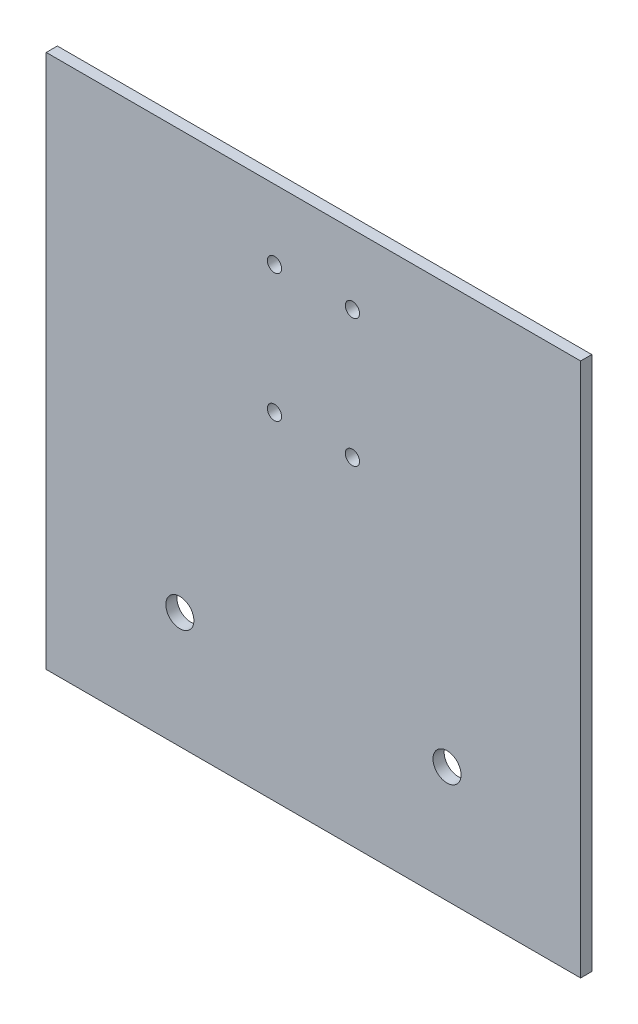
SolidWorks part; units mm, degrees
ref_plane "Front Plane" through (0, 0, 0) normal (0, 0, 1) x (1, 0, 0)
ref_plane "Top Plane" through (0, 0, 0) normal (0, 1, 0) x (1, 0, 0)
ref_plane "Right Plane" through (0, 0, 0) normal (1, 0, 0) x (0, 0, -1)
sketch "Sketch1" plane through (0, 0, 0) normal (0, 0, 1) x (1, 0, 0)
  line L1 (76.2, -76.2) -> (-76.2, -76.2)
  line L2 (76.2, -76.2) -> (76.2, 76.2)
  line L3 (76.2, 76.2) -> (-76.2, 76.2)
  line L4 (-76.2, -76.2) -> (-76.2, 76.2)
  line L5 (76.2, -76.2) -> (-76.2, 76.2) construction
  line L6 (76.2, 76.2) -> (-76.2, -76.2) construction
  point P0 (0, 0)
extrude "Boss-Extrude1" add sketch "Sketch1" along normal blind 3.175
sketch "Sketch2" plane through (0, 0, 3.175) normal (0, 0, 1) x (1, 0, 0)
  line L0 (-76.2, 76.2) -> (-76.2, -76.2) construction
  line L1 (-16.6613, 15.8694) -> (16.6613, 15.8694)
  line L2 (-16.6613, 15.8694) -> (-16.6613, 60.3306)
  line L3 (-16.6613, 60.3306) -> (16.6613, 60.3306)
  line L4 (16.6613, 15.8694) -> (16.6613, 60.3306)
  line L5 (-16.6613, 15.8694) -> (16.6613, 60.3306) construction
  line L6 (-16.6613, 60.3306) -> (16.6613, 15.8694) construction
  line L7 (-11.1125, 19.8374) -> (11.1125, 19.8374)
  line L8 (-11.1125, 19.8374) -> (-11.1125, 56.3626)
  line L9 (-11.1125, 56.3626) -> (11.1125, 56.3626)
  line L10 (11.1125, 19.8374) -> (11.1125, 56.3626)
  line L11 (-11.1125, 19.8374) -> (11.1125, 56.3626) construction
  line L12 (-11.1125, 56.3626) -> (11.1125, 19.8374) construction
  line L13 (76.2, -76.2) -> (76.2, 76.2) construction
  line L14 (76.2, 76.2) -> (-76.2, 76.2) construction
  circle A0 centre (-38.1, -43.0951) radius 4
  circle A1 centre (38.1, -43.0951) radius 4
  circle A3 centre (-11.1125, 56.3626) radius 2.032
  circle A4 centre (11.1125, 56.3626) radius 2.032
  circle A5 centre (11.1125, 19.8374) radius 2.032
  circle A6 centre (-11.1125, 19.8374) radius 2.032
  point P0 (0, 38.1)
  point P5 (0, 38.1)
  dimension "D2" = 38.1
  dimension "D4" = 38.1
  dimension "D1" = 76.2
  dimension "D3" = 38.1
extrude "Cut-Extrude2" cut sketch "Sketch2" against normal blind 42.418 and the other way blind 2.54 contours A3 | A4 | A5 | A6
extrude "Cut-Extrude3" cut sketch "Sketch2<5>" against normal blind 42.418 contours A0 | A1 region at (-38.1, -43.0951, 3.175) region at (38.1, -43.0951, 3.175)
sketch "Sketch2<5>" plane through (0, 0, 3.175) normal (0, 0, 1) x (1, 0, 0) same geometry as "Sketch2"
